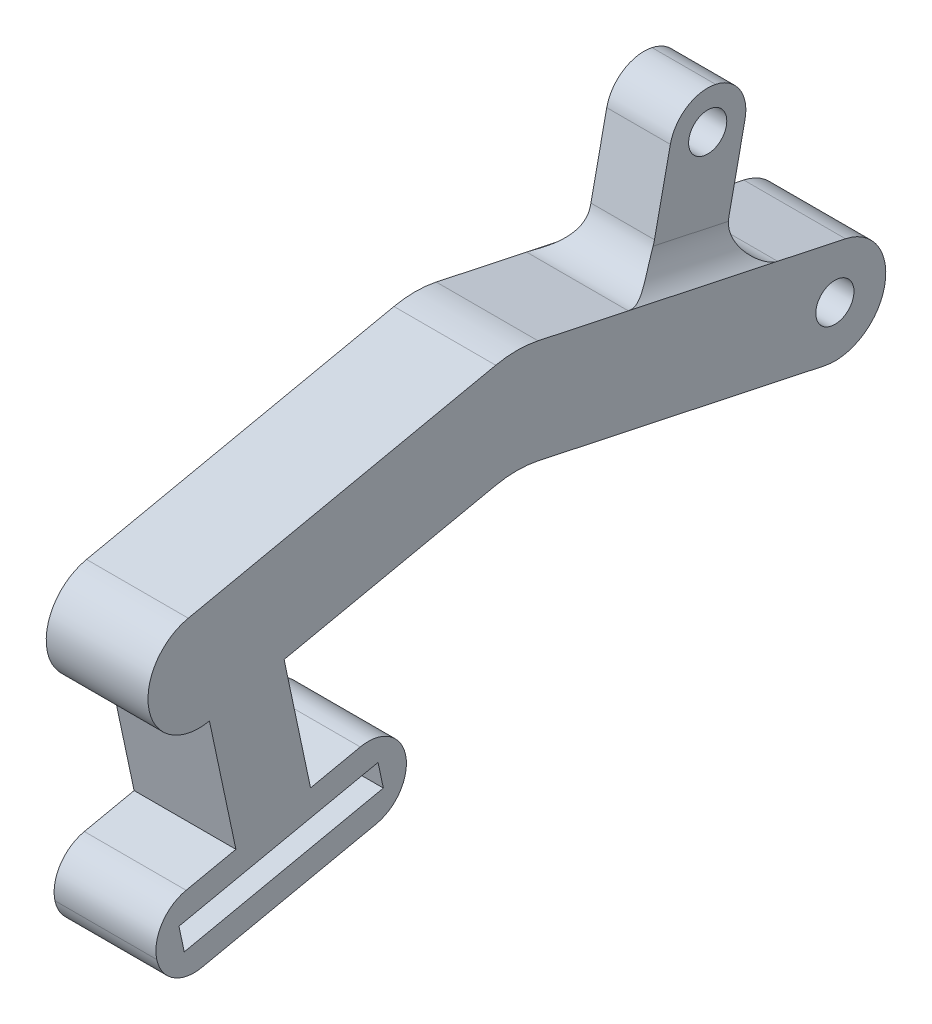
SolidWorks part; units mm, degrees
ref_plane "Alzado" through (0, 0, 0) normal (0, 0, 1) x (1, 0, 0)
ref_plane "Planta" through (0, 0, 0) normal (0, 1, 0) x (1, 0, 0)
ref_plane "Vista lateral" through (0, 0, 0) normal (1, 0, 0) x (0, 0, -1)
sketch "Croquis1" plane through (0, 0, 0) normal (1, 0, 0) x (0, 0, -1)
  line L0 (-25.8316, 3.9126) -> (0, 9.4033) construction
  line L9 (0, 9.4033) -> (25.8316, 3.9126) construction
  line L10 (-24.1684, -3.9126) -> (0, 1.2246) construction
  line L15 (-25, 0) -> (25, 0) construction
  line L16 (0, 1.2246) -> (24.1684, -3.9126) construction
  line L17 (-25.8316, 3.9126) -> (-1.6633, 9.0497)
  line L18 (1.6633, 9.0497) -> (25.8316, 3.9126)
  line L19 (-24.1684, -3.9126) -> (-1.6633, 0.871)
  line L20 (1.6633, 0.871) -> (24.1684, -3.9126)
  circle A4 centre (25, 0) radius 1.5
  arc A7 (-25.8316, 3.9126) -> (-24.1684, -3.9126) centre (-25, 0) ccw
  arc A8 (24.1684, -3.9126) -> (25.8316, 3.9126) centre (25, 0) ccw
  arc A9 (-1.6633, 9.0497) -> (1.6633, 9.0497) centre (0, 1.2246) cw
  arc A10 (-1.6633, 0.871) -> (1.6633, 0.871) centre (0, -6.9542) cw
  point P0 (0, 0)
  point P1 (0, 0)
  dimension "D4" = 3
  dimension "D2" = 8
  dimension "D5" = 8
  dimension "D1" = 25
  dimension "D3" = 12
  dimension "D7" = 12
extrude "Saliente-Extruir1" add sketch "Croquis1" along normal mid plane 8
sketch "Croquis11" plane through (0, 8.9968, -1.9123) normal (0, 0.9781, -0.2079) x (1, 0, 0)
  line L8 (-2.5, 10) -> (2.5, 10)
  line L9 (-2.5, 10) -> (-2.5, 16)
  line L10 (-2.5, 16) -> (2.5, 16)
  line L11 (2.5, 10) -> (2.5, 16)
  point P4 (0, 10)
  dimension "D1" = 10
  dimension "D2" = 6
  dimension "D3" = 5
extrude "Saliente-Extruir6" add sketch "Croquis11" along normal blind 12
fillet "Redondeo3" radius 3 4 edges at (2.5, 6.2939, -14.6282) (0, 6.9177, -11.6938) (0, 5.6702, -17.5627) (-2.5, 6.2939, -14.6282)
fillet "Redondeo4" radius 3 2 edges at (0, 18.6555, -14.1887) (0, 17.408, -20.0576)
sketch "Croquis12" plane through (0, 0, 0) normal (1, 0, 0) x (0, 0, -1)
  circle A0 centre (16.4995, 15.0973) radius 1.5
  dimension "D1" = 3
extrude "Cortar-Extruir4" cut sketch "Croquis12" against normal through all both and the other way through all
sketch "Croquis8" plane through (0, 1.1716, 0.249) normal (0, -0.9781, -0.2079) x (1, 0, 0)
  line L0 (4, 24.4537) -> (4, 1.4459) construction
  line L1 (-4, 24.4537) -> (4, 24.4537)
  line L2 (-4, 24.4537) -> (-4, 18.4537)
  line L3 (-4, 18.4537) -> (4, 18.4537)
  line L4 (4, 24.4537) -> (4, 18.4537)
  dimension "D1" = 6
extrude "Saliente-Extruir4" add sketch "Croquis8" along normal blind 10
sketch "Croquis9" plane through (0, -8.6099, -1.8301) normal (0, -0.9781, -0.2079) x (1, 0, 0)
  line L0 (-4, 18.4537) -> (-4, 1.4459) construction
  line L1 (-4, 11.4537) -> (4, 11.4537)
  line L2 (-4, 11.4537) -> (-4, 31.4537)
  line L3 (-4, 31.4537) -> (4, 31.4537)
  line L4 (4, 11.4537) -> (4, 31.4537)
  line L5 (4, 18.4537) -> (4, 1.4459) construction
  line L6 (4, 24.4537) -> (-4, 24.4537) construction
  dimension "D1" = 20
  dimension "D2" = 7
extrude "Saliente-Extruir5" add sketch "Croquis9" along normal blind 6
sketch "Croquis10" plane through (-4, 0, 0) normal (-1, 0, 0) x (0, 0, 1)
  line L0 (22.0892, -13.6941) -> (16.2204, -12.4466) construction
  line L1 (21.6734, -15.6504) -> (15.8045, -14.4029)
  line L2 (15.8045, -14.4029) -> (10.9138, -13.3633)
  line L3 (10.9138, -13.3633) -> (10.498, -15.3196)
  line L4 (10.498, -15.3196) -> (26.1483, -18.6462)
  line L5 (26.1483, -18.6462) -> (26.5642, -16.6899)
  line L6 (26.5642, -16.6899) -> (21.6734, -15.6504)
  line L12 (-1.6633, 9.0497) -> (-8.7594, 7.5414)
  line L13 (-8.7594, 7.5414) -> (-20.4971, 5.0465)
  line L14 (-24.1684, -3.9126) -> (-1.6633, 0.871)
  line L15 (1.6633, 0.871) -> (18.2995, -2.6651)
  line L16 (18.2995, -2.6651) -> (16.2204, -12.4466)
  line L17 (16.2204, -12.4466) -> (9.3733, -10.9912)
  line L18 (9.3733, -10.9912) -> (8.1258, -16.8601)
  line L19 (8.1258, -16.8601) -> (27.6888, -21.0183)
  line L20 (27.6888, -21.0183) -> (28.9363, -15.1494)
  line L21 (28.9363, -15.1494) -> (22.0892, -13.6941)
  line L22 (22.0892, -13.6941) -> (24.1684, -3.9126)
  line L23 (25.8316, 3.9126) -> (1.6633, 9.0497)
  line L29 (16.2204, -12.4466) -> (9.3733, -10.9912) construction
  line L30 (9.3733, -10.9912) -> (8.1258, -16.8601) construction
  line L31 (8.1258, -16.8601) -> (27.6888, -21.0183) construction
  line L32 (27.6888, -21.0183) -> (28.9363, -15.1494) construction
  line L33 (28.9363, -15.1494) -> (22.0892, -13.6941) construction
  line L44 (-20.4971, 5.0465) -> (-25.8316, 3.9126)
  arc A3 (1.6633, 0.871) -> (-1.6633, 0.871) centre (0, -6.9542) ccw
  arc A4 (24.1684, -3.9126) -> (25.8316, 3.9126) centre (25, 0) ccw
  arc A5 (1.6633, 9.0497) -> (-1.6633, 9.0497) centre (0, 1.2246) ccw
  arc A7 (-25.8316, 3.9126) -> (-24.1684, -3.9126) centre (-25, 0) ccw
  dimension "D1" = 0
  dimension "D2" = 2
extrude "Cortar-Extruir3" cut sketch "Croquis10" against normal through all
fillet "Redondeo2" radius 3 4 edges at (0, -21.0183, 27.6888) (0, -16.8601, 8.1258) (0, -10.9912, 9.3733) (0, -15.1494, 28.9363)
